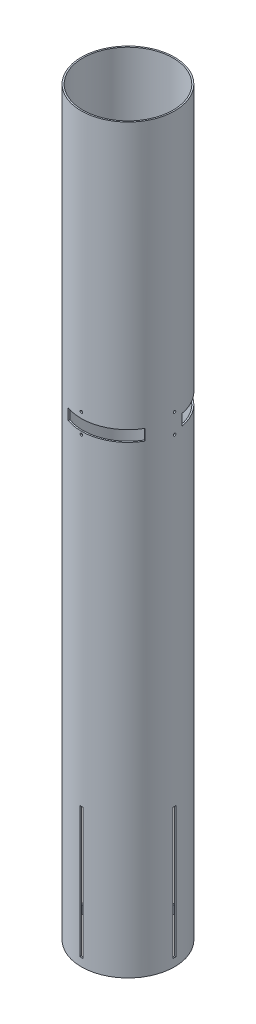
SolidWorks part; units mm, degrees
material "A-Glass Fiber"
ref_plane "Front Plane" through (0, 0, 0) normal (0, 0, 1) x (1, 0, 0)
ref_plane "Top Plane" through (0, 0, 0) normal (0, 1, 0) x (1, 0, 0)
ref_plane "Right Plane" through (0, 0, 0) normal (1, 0, 0) x (0, 0, -1)
sketch "Sketch1" plane through (0, 0, 0) normal (0, 1, 0) x (1, 0, 0)
  circle A0 centre (0, 0) radius 49.53
  circle A1 centre (0, 0) radius 51.1048
  dimension "D1" = 99.06
  dimension "D2" = 102.2096
extrude "Boss-Extrude1" add sketch "Sketch1" along normal blind 812.8
ref_plane "Plane1" through (0, 0, 0) normal (0.7071, 0, 0.7071) x (0.7071, 0, -0.7071)
ref_axis "Axis1" through (0, 812.8, 0) along (0, -1, 0)
sketch "Sketch2" plane through (0, 0, 0) normal (1, 0, 0) x (0, 0, -1)
  line L0 (0, 0) -> (0, 8.89)
  line L1 (1.5875, 8.89) -> (-1.5875, 8.89)
  line L2 (1.5875, 8.89) -> (1.5875, 152.4)
  line L3 (1.5875, 152.4) -> (-1.5875, 152.4)
  line L4 (-1.5875, 8.89) -> (-1.5875, 152.4)
  line L5 (1.5875, 8.89) -> (-1.5875, 152.4) construction
  line L6 (1.5875, 152.4) -> (-1.5875, 8.89) construction
  line L7 (51.1048, 812.8) -> (-51.1048, 812.8) construction
  line L8 (51.1048, 812.8) -> (-51.1048, 812.8)
  line L9 (0, 812.8) -> (0, 527.05)
  line L10 (-51.1048, 0) -> (51.1048, 0) construction
  circle A0 centre (0, 527.05) radius 1.3525
  point P0 (0, 80.645)
  dimension "D4" = 2.7051
  dimension "D1" = 3.175
  dimension "D5" = 527.05
  dimension "D3" = 152.4
  dimension "D2" = 8.89
extrude "Cut-Extrude1" cut sketch "Sketch2" against normal through all contours L4 L1 L2 L3 region at (0, 80.645, 0)
pattern_circular "CirPattern1" count 4 over 360 about axis through (0, 0, 0) along (0, 1, 0) of "Cut-Extrude1" reverse direction yes
extrude "Cut-Extrude2" cut sketch "Sketch2<3>" against normal through all contours A0 region at (0, 526.1207, 0.9293)
sketch "Sketch2<3>" plane through (0, 0, 0) normal (1, 0, 0) x (0, 0, -1) same geometry as "Sketch2"
pattern_circular "CirPattern2" count 4 over 360 about axis through (0, 812.8, 0) along (0, -1, 0) of "Cut-Extrude2"
sketch "Sketch3" plane through (0, 0, 0) normal (0.7071, 0, 0.7071) x (0.7071, 0, -0.7071)
  line L0 (0, 0) -> (0, 127) construction
  circle A0 centre (0, 127) radius 3.175
  dimension "D1" = 6.35
  dimension "D2" = 127
extrude "Cut-Extrude3" cut sketch "Sketch3" against normal through all
sketch "Sketch7" plane through (0, 0, 0) normal (0, 1, 0) x (1, 0, 0)
  line L0 (0, 0) -> (-44.2581, -25.5524)
  line L1 (0, 0) -> (0, 93.232) construction
  line L2 (0, 0) -> (-32.8495, 39.1485)
  line L3 (-51.1048, 0) -> (0, 0) construction
  arc A0 (-51.0869, 1.3525) -> (-51.0869, -1.3525) centre (0, 0) ccw construction
  circle A1 centre (0, 0) radius 49.53 construction
  circle A2 centre (0, 0) radius 51.1048
  circle A3 centre (0, 0) radius 51.1048
  circle A4 centre (0, 0) radius 49.53
  circle A5 centre (0, 0) radius 51.1048 construction
  arc A6 (1.3526, 51.0869) -> (-1.3525, 51.0869) centre (0, 0) ccw construction
  arc A7 (-51.0869, 1.3525) -> (-51.0869, -1.3525) centre (0, 0) ccw
  arc A8 (1.3526, 51.0869) -> (-1.3525, 51.0869) centre (0, 0) ccw
  dimension "D1" = 80
  dimension "D3" = 30
  dimension "D2" = 0
extrude "Cut-Extrude4" cut sketch "Sketch7" against normal blind 12.065 from offset 520.7 contours A4 A3 L0 region at (-43.9137, 0, 24.5741)
pattern_circular "CirPattern3" count 3 over 360 about axis through (0, 812.8, 0) along (0, -1, 0) of "Cut-Extrude4"
pattern_linear "LPattern1" count 2 spacing 21.6916 along (0, -1, 0) of "CirPattern2"
equation "\"D1@Boss-Extrude1\" = \"Aft_Section_Length\""
equation "\"AB_Coupler_OD_Length\"= 1in"
equation "\"AB_Coupling_Section_Length\"= 0.375in"
equation "\"AB_Coupler_Length\"= \"AB_Coupler_OD_Length\" + \"AB_Coupling_Section_Length\" * 2"
equation "\"AB_Coupler_Num_Screws\"= 4"
equation "\"AB_Coupling_Screw_Diameter\"= 0.1065in"
equation "\"Aft_Section_Length\" = 32in"
equation "\"D4@Sketch2\"=\"AB_Coupling_Screw_Diameter\""
equation "\"D1@CirPattern2\"=\"AB_Coupler_Num_Screws\""
equation "\"Rail_Nut_From_Bottom\"= 5in"
equation "\"Rail_Nut_Diam\"= 0.25in"
equation "\"D1@Sketch3\"=\"Rail_Nut_Diam\""
equation "\"D2@Sketch3\"=\"Rail_Nut_From_Bottom\""
equation "\"AB_BKHD_Thickness\"= 0.375in"
equation "\"AB_Mount_From_Bottom\"= 20.75in"
equation "\"Cutout_Angle\" = 60"
equation "\"Motor_OD\" = 54.4mm"
equation "\"Motor_Length\" = 401mm"
equation "\"Mid_Coupler_Length\" = 12in"
equation "\"AB_Paddle_Height\" = 0.375in"
equation "\"Num_Cutouts\" = 4"
equation "\"AB_Coupler_OD\"= 4.024in"
equation "\"AB_Coupler_ID\"= 3.7in"
equation "\"AB_Coupler_Surface_Diameter\"= 3.899in"
equation "\"AB_Central_Bushing_Length\" = 0.75in"
equation "\"Lead_Screw_Dist\" = 2in"
equation "\"Lead_Screw_Diam\" = 0.375in"
equation "\"Lead_Screw_Length\" = \"Mid_Coupler_Length\" + 2*0.375in + 2*0.5in"
equation "\"Paddle_Pin_Offset\" = 0.25in"
equation "\"Paddle_Pin_Radius\" = 2.25*2/3in"
equation "\"Paddle_Gear_OD\" = 3.2in"
equation "\"Fwd_BKHD_From_Top\" = 18in"
equation "\"Body_Tube_OD\"= 4.024in"
equation "\"Body_Tube_ID\"= 3.90in"
equation "\"Coupler_OD\" = 3.899in"
equation "\"Coupler_ID\" = 3.755in"
equation "\"Fwd_Section_Length\" = 20in"
equation "\"Mid_Section_Length\" = 4in"
equation "\"Aft_Upper_Tube_Length\" = 10in"
equation "\"Aft_Lower_Tube_Length\" = 18in"
equation "\"Nosecone_Coupler_Length\" = 5in"
equation "\"Avionics_Bulkhead_Thickness\" = 0.25in"
equation "\"Avionics_Bulkhead_Lip\" = 0.125in"
equation "\"Avionics_Board_Length\" = \"Mid_Coupler_Length\" - 2*\"Avionics_Bulkhead_Lip\""
equation "\"Lead_Screw_Hole_Diam\" = 0.386in"
equation "\"Centering_Ring_Cutout_Dia\"=1.5in"
equation "\"D2@Sketch1\"=\"Body_Tube_OD\""
equation "\"D1@Sketch1\"=\"Body_Tube_ID\""
equation "\"D5@Sketch2\"=\"AB_Mount_From_Bottom\""
equation "\"D19@Cut-Extrude4\"=\"AB_Mount_From_Bottom\"-0.25"
